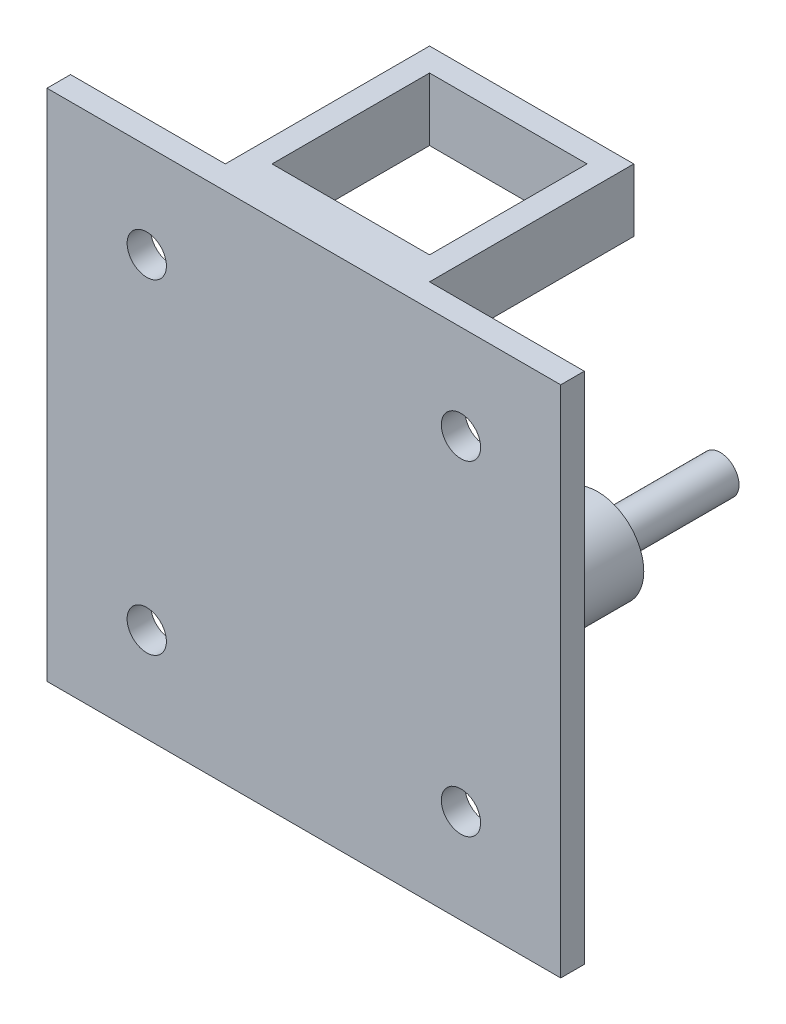
SolidWorks part; units mm, degrees
ref_plane "Спереди" through (0, 0, 0) normal (0, 0, 1) x (1, 0, 0)
ref_plane "Сверху" through (0, 0, 0) normal (0, 1, 0) x (1, 0, 0)
ref_plane "Справа" through (0, 0, 0) normal (1, 0, 0) x (0, 0, -1)
sketch "Эскиз1" plane through (0, 0, 0) normal (0, 0, 1) x (1, 0, 0)
  line L0 (-65.4, 53.4) -> (0, 53.4) construction
  line L1 (0, 0) -> (-65.4, 0)
  line L2 (0, 0) -> (0, 65.4)
  line L3 (0, 65.4) -> (-65.4, 65.4)
  line L4 (-65.4, 0) -> (-65.4, 65.4)
  line L5 (-32.7, 65.4) -> (-32.7, 0) construction
  line L6 (-65.4, 32.7) -> (0, 32.7) construction
  circle A0 centre (-52.7, 53.4) radius 2.5
  circle A2 centre (-12.7, 53.4) radius 2.5
  circle A3 centre (-12.7, 12) radius 2.5
  circle A4 centre (-52.7, 12) radius 2.5
  dimension "D4" = 5
  dimension "D5" = 20
  dimension "D1" = 65.4
  dimension "D2" = 65.4
  dimension "D3" = 12
extrude "каретка" add sketch "Эскиз1" along normal blind 3
sketch "Эскиз2" plane through (0, 0, 0) normal (0, 0, -1) x (-1, 0, 0)
  line L0 (0, 65.4) -> (65.4, 65.4) construction
  line L1 (19.7, 65.4) -> (45.7, 65.4)
  line L2 (19.7, 65.4) -> (19.7, 57.4)
  line L3 (19.7, 57.4) -> (45.7, 57.4)
  line L4 (45.7, 65.4) -> (45.7, 57.4)
  line L5 (32.7, 65.4) -> (32.7, 0) construction
  line L6 (65.4, 0) -> (0, 0) construction
  point P10 (32.7, 65.4)
  dimension "D1" = 8
  dimension "D2" = 26
extrude "крепеж для направляющей" add sketch "Эскиз2" along normal blind 26
sketch "Эскиз3" plane through (0, 57.4, 0) normal (0, -1, 0) x (1, 0, 0)
  line L0 (-45.7, -13) -> (-19.7, -13) construction
  line L1 (-42.725, -2.975) -> (-22.675, -2.975)
  line L2 (-42.725, -2.975) -> (-42.725, -23.025)
  line L3 (-42.725, -23.025) -> (-22.675, -23.025)
  line L4 (-22.675, -2.975) -> (-22.675, -23.025)
  line L5 (-45.7, -26) -> (-45.7, 0) construction
  line L6 (-19.7, -26) -> (-19.7, 0) construction
  line L7 (-42.725, -13) -> (-22.675, -13) construction
  point P12 (-32.7, -13)
  point P13 (-32.7, -13)
  dimension "D1" = 20.05
  dimension "D2" = 20.05
extrude "дырка в крепеже для направляющей" cut sketch "Эскиз3" against normal through all
sketch "Эскиз4" plane through (0, 0, 0) normal (0, 0, -1) x (-1, 0, 0)
  line L0 (12.7, 53.4) -> (12.7, 12) construction
  line L1 (52.7, 53.4) -> (52.7, 12) construction
  circle A1 centre (52.7, 32.7) radius 2
  point P6 (52.7, 32.7)
  dimension "D1" = 4
sketch "Эскиз5" plane through (0, 0, 0) normal (0, 0, -1) x (-1, 0, 0)
  line L0 (52.7, 53.4) -> (52.7, 12) construction
  line L1 (12.7, 53.4) -> (12.7, 12) construction
  circle A0 centre (12.7, 32.7) radius 2.4
  point P10 (12.7, 32.7)
  dimension "D1" = 4.8
sketch "Эскиз8" plane through (0, 0, 0) normal (0, 0, -1) x (-1, 0, 0)
  line L0 (12.7, 53.4) -> (12.7, 12) construction
  circle A0 centre (12.7, 32.7) radius 5.8726
  point P7 (12.7, 32.7)
  dimension "D1" = 11.7451
extrude "Бобышка-Вытянуть1" add sketch "Эскиз8" along normal blind 14.4
extrude "Бобышка-Вытянуть2" add sketch "Эскиз5" along normal blind 30
extrude "Бобышка-Вытянуть3" add sketch "Эскиз4" along normal blind 14.4 contours A1
sketch "Эскиз12" plane through (0, 0, 0) normal (0, 0, -1) x (-1, 0, 0)
  circle A0 centre (52.7, 32.7) radius 5
  dimension "D1" = 10
extrude "Бобышка-Вытянуть5" add sketch "Эскиз12" along normal blind 21 contours A0
sketch "Эскиз13" plane through (0, 0, -21) normal (0, 0, -1) x (-1, 0, 0)
  circle A0 centre (52.7, 32.7) radius 2
  dimension "D1" = 4
extrude "Вырез-Вытянуть1" cut sketch "Эскиз13" against normal blind 6.6
